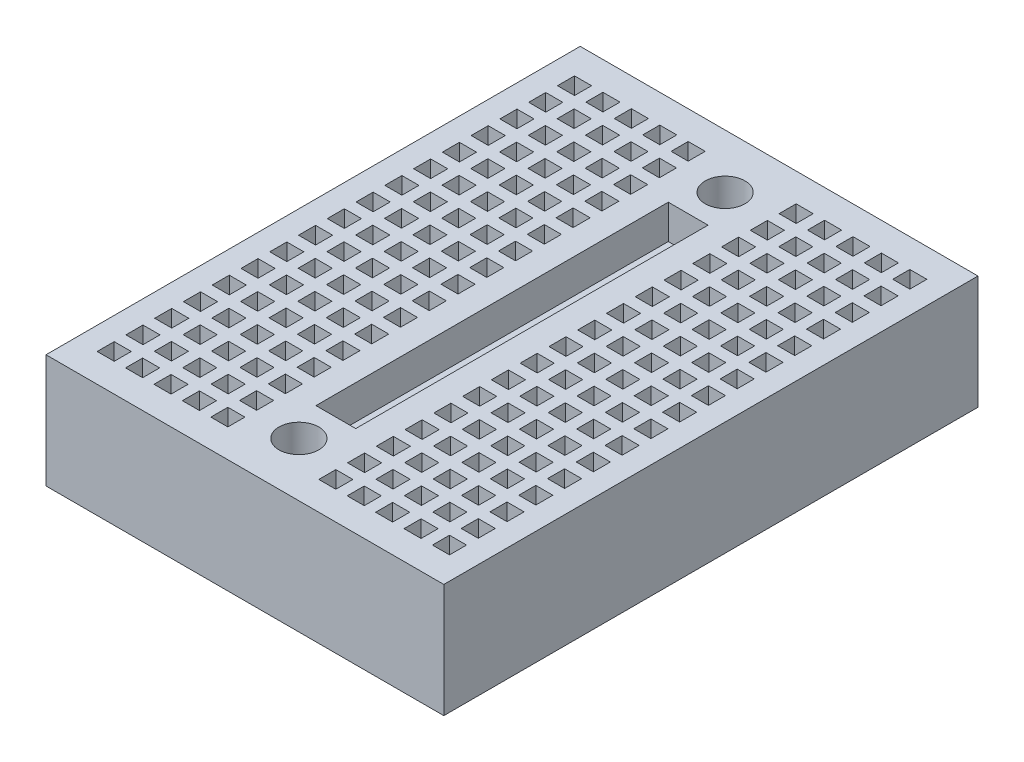
SolidWorks part; units mm, degrees
ref_plane "Front Plane" through (0, 0, 0) normal (0, 0, 1) x (1, 0, 0)
ref_plane "Top Plane" through (0, 0, 0) normal (0, 1, 0) x (1, 0, 0)
ref_plane "Right Plane" through (0, 0, 0) normal (1, 0, 0) x (0, 0, -1)
sketch "Sketch2" plane through (0, 0, 0) normal (0, 1, 0) x (1, 0, 0)
  line L1 (0, 23.5) -> (-17.5, 23.5)
  line L2 (0, 23.5) -> (0, -23.5)
  line L3 (0, -23.5) -> (-17.5, -23.5)
  line L4 (-17.5, 23.5) -> (-17.5, -23.5)
  line L5 (0, 23.5) -> (-17.5, -23.5) construction
  line L6 (0, -23.5) -> (-17.5, 23.5) construction
  point P0 (0, 0)
  point P6 (0, 0)
  point P7 (0, 0)
  dimension "D1" = 17.5
  dimension "D2" = 47
extrude "Boss-Extrude1" add sketch "Sketch2" along normal blind 7
sketch "Sketch3" plane through (0, 7, 0) normal (0, 1, 0) x (1, 0, 0)
  line L0 (0, -23.5) -> (0, 23.5) construction
  line L5 (1.75, -15.5) -> (-1.75, -15.5)
  line L6 (1.75, -15.5) -> (1.75, 15.5)
  line L7 (0, 23.5) -> (-17.5, 23.5) construction
  line L8 (-17.5, -23.5) -> (0, -23.5) construction
  line L9 (1.75, 15.5) -> (-1.75, 15.5)
  line L10 (-1.75, -15.5) -> (-1.75, 15.5)
  line L12 (-13, 21) -> (-13, 19.5)
  line L13 (-15.5, 21) -> (-14, 21)
  line L14 (-15.5, 21) -> (-15.5, 19.5)
  line L15 (-15.5, 19.5) -> (-14, 19.5)
  line L16 (-14, 21) -> (-14, 19.5)
  line L17 (-13, 21) -> (-11.5, 21)
  line L18 (-11.5, 21) -> (-11.5, 19.5)
  line L19 (-13, 19.5) -> (-11.5, 19.5)
  line L20 (-10.5, 21) -> (-10.5, 19.5)
  line L21 (-10.5, 21) -> (-9, 21)
  line L22 (-9, 21) -> (-9, 19.5)
  line L23 (-10.5, 19.5) -> (-9, 19.5)
  line L24 (-8, 21) -> (-8, 19.5)
  line L25 (-8, 21) -> (-6.5, 21)
  line L26 (-6.5, 21) -> (-6.5, 19.5)
  line L27 (-8, 19.5) -> (-6.5, 19.5)
  line L28 (-5.5, 21) -> (-5.5, 19.5)
  line L29 (-5.5, 21) -> (-4, 21)
  line L30 (-4, 21) -> (-4, 19.5)
  line L31 (-5.5, 19.5) -> (-4, 19.5)
  line L32 (-13, 18.4688) -> (-13, 16.9687)
  line L33 (-13, 18.4688) -> (-11.5, 18.4688)
  line L34 (-11.5, 18.4688) -> (-11.5, 16.9687)
  line L35 (-13, 16.9687) -> (-11.5, 16.9687)
  line L36 (-10.5, 18.4688) -> (-10.5, 16.9687)
  line L37 (-10.5, 18.4688) -> (-9, 18.4688)
  line L38 (-9, 18.4688) -> (-9, 16.9687)
  line L39 (-10.5, 16.9687) -> (-9, 16.9687)
  line L40 (-8, 18.4688) -> (-8, 16.9687)
  line L41 (-8, 18.4688) -> (-6.5, 18.4688)
  line L42 (-6.5, 18.4688) -> (-6.5, 16.9687)
  line L43 (-8, 16.9687) -> (-6.5, 16.9687)
  line L44 (-5.5, 18.4688) -> (-5.5, 16.9687)
  line L45 (-5.5, 18.4688) -> (-4, 18.4688)
  line L46 (-4, 18.4688) -> (-4, 16.9687)
  line L47 (-5.5, 16.9687) -> (-4, 16.9687)
  line L48 (-13, 15.9375) -> (-13, 14.4375)
  line L49 (-13, 15.9375) -> (-11.5, 15.9375)
  line L50 (-11.5, 15.9375) -> (-11.5, 14.4375)
  line L51 (-13, 14.4375) -> (-11.5, 14.4375)
  line L52 (-10.5, 15.9375) -> (-10.5, 14.4375)
  line L53 (-10.5, 15.9375) -> (-9, 15.9375)
  line L54 (-9, 15.9375) -> (-9, 14.4375)
  line L55 (-10.5, 14.4375) -> (-9, 14.4375)
  line L56 (-8, 15.9375) -> (-8, 14.4375)
  line L57 (-8, 15.9375) -> (-6.5, 15.9375)
  line L58 (-6.5, 15.9375) -> (-6.5, 14.4375)
  line L59 (-8, 14.4375) -> (-6.5, 14.4375)
  line L60 (-5.5, 15.9375) -> (-5.5, 14.4375)
  line L61 (-5.5, 15.9375) -> (-4, 15.9375)
  line L62 (-4, 15.9375) -> (-4, 14.4375)
  line L63 (-5.5, 14.4375) -> (-4, 14.4375)
  line L64 (-13, 13.4063) -> (-13, 11.9062)
  line L65 (-13, 13.4063) -> (-11.5, 13.4063)
  line L66 (-11.5, 13.4063) -> (-11.5, 11.9062)
  line L67 (-13, 11.9062) -> (-11.5, 11.9062)
  line L68 (-10.5, 13.4063) -> (-10.5, 11.9062)
  line L69 (-10.5, 13.4063) -> (-9, 13.4063)
  line L70 (-9, 13.4063) -> (-9, 11.9062)
  line L71 (-10.5, 11.9062) -> (-9, 11.9062)
  line L72 (-8, 13.4063) -> (-8, 11.9062)
  line L73 (-8, 13.4063) -> (-6.5, 13.4063)
  line L74 (-6.5, 13.4063) -> (-6.5, 11.9062)
  line L75 (-8, 11.9062) -> (-6.5, 11.9062)
  line L76 (-5.5, 13.4063) -> (-5.5, 11.9062)
  line L77 (-5.5, 13.4063) -> (-4, 13.4063)
  line L78 (-4, 13.4063) -> (-4, 11.9062)
  line L79 (-5.5, 11.9062) -> (-4, 11.9062)
  line L80 (-13, 10.875) -> (-13, 9.375)
  line L81 (-13, 10.875) -> (-11.5, 10.875)
  line L82 (-11.5, 10.875) -> (-11.5, 9.375)
  line L83 (-13, 9.375) -> (-11.5, 9.375)
  line L84 (-10.5, 10.875) -> (-10.5, 9.375)
  line L85 (-10.5, 10.875) -> (-9, 10.875)
  line L86 (-9, 10.875) -> (-9, 9.375)
  line L87 (-10.5, 9.375) -> (-9, 9.375)
  line L88 (-8, 10.875) -> (-8, 9.375)
  line L89 (-8, 10.875) -> (-6.5, 10.875)
  line L90 (-6.5, 10.875) -> (-6.5, 9.375)
  line L91 (-8, 9.375) -> (-6.5, 9.375)
  line L92 (-5.5, 10.875) -> (-5.5, 9.375)
  line L93 (-5.5, 10.875) -> (-4, 10.875)
  line L94 (-4, 10.875) -> (-4, 9.375)
  line L95 (-5.5, 9.375) -> (-4, 9.375)
  line L96 (-13, 8.3438) -> (-13, 6.8438)
  line L97 (-13, 8.3438) -> (-11.5, 8.3438)
  line L98 (-11.5, 8.3438) -> (-11.5, 6.8438)
  line L99 (-13, 6.8438) -> (-11.5, 6.8438)
  line L100 (-10.5, 8.3438) -> (-10.5, 6.8438)
  line L101 (-10.5, 8.3438) -> (-9, 8.3438)
  line L102 (-9, 8.3438) -> (-9, 6.8438)
  line L103 (-10.5, 6.8438) -> (-9, 6.8438)
  line L104 (-8, 8.3438) -> (-8, 6.8438)
  line L105 (-8, 8.3438) -> (-6.5, 8.3438)
  line L106 (-6.5, 8.3438) -> (-6.5, 6.8438)
  line L107 (-8, 6.8438) -> (-6.5, 6.8438)
  line L108 (-5.5, 8.3438) -> (-5.5, 6.8438)
  line L109 (-5.5, 8.3438) -> (-4, 8.3438)
  line L110 (-4, 8.3438) -> (-4, 6.8438)
  line L111 (-5.5, 6.8438) -> (-4, 6.8438)
  line L112 (-13, 5.8125) -> (-13, 4.3125)
  line L113 (-13, 5.8125) -> (-11.5, 5.8125)
  line L114 (-11.5, 5.8125) -> (-11.5, 4.3125)
  line L115 (-13, 4.3125) -> (-11.5, 4.3125)
  line L116 (-10.5, 5.8125) -> (-10.5, 4.3125)
  line L117 (-10.5, 5.8125) -> (-9, 5.8125)
  line L118 (-9, 5.8125) -> (-9, 4.3125)
  line L119 (-10.5, 4.3125) -> (-9, 4.3125)
  line L120 (-8, 5.8125) -> (-8, 4.3125)
  line L121 (-8, 5.8125) -> (-6.5, 5.8125)
  line L122 (-6.5, 5.8125) -> (-6.5, 4.3125)
  line L123 (-8, 4.3125) -> (-6.5, 4.3125)
  line L124 (-5.5, 5.8125) -> (-5.5, 4.3125)
  line L125 (-5.5, 5.8125) -> (-4, 5.8125)
  line L126 (-4, 5.8125) -> (-4, 4.3125)
  line L127 (-5.5, 4.3125) -> (-4, 4.3125)
  line L128 (-13, 3.2813) -> (-13, 1.7813)
  line L129 (-13, 3.2813) -> (-11.5, 3.2813)
  line L130 (-11.5, 3.2813) -> (-11.5, 1.7813)
  line L131 (-13, 1.7813) -> (-11.5, 1.7813)
  line L132 (-10.5, 3.2813) -> (-10.5, 1.7813)
  line L133 (-10.5, 3.2813) -> (-9, 3.2813)
  line L134 (-9, 3.2813) -> (-9, 1.7813)
  line L135 (-10.5, 1.7813) -> (-9, 1.7813)
  line L136 (-8, 3.2813) -> (-8, 1.7813)
  line L137 (-8, 3.2813) -> (-6.5, 3.2813)
  line L138 (-6.5, 3.2813) -> (-6.5, 1.7813)
  line L139 (-8, 1.7813) -> (-6.5, 1.7813)
  line L140 (-5.5, 3.2813) -> (-5.5, 1.7813)
  line L141 (-5.5, 3.2813) -> (-4, 3.2813)
  line L142 (-4, 3.2813) -> (-4, 1.7813)
  line L143 (-5.5, 1.7813) -> (-4, 1.7813)
  line L144 (-13, 0.75) -> (-13, -0.75)
  line L145 (-13, 0.75) -> (-11.5, 0.75)
  line L146 (-11.5, 0.75) -> (-11.5, -0.75)
  line L147 (-13, -0.75) -> (-11.5, -0.75)
  line L148 (-10.5, 0.75) -> (-10.5, -0.75)
  line L149 (-10.5, 0.75) -> (-9, 0.75)
  line L150 (-9, 0.75) -> (-9, -0.75)
  line L151 (-10.5, -0.75) -> (-9, -0.75)
  line L152 (-8, 0.75) -> (-8, -0.75)
  line L153 (-8, 0.75) -> (-6.5, 0.75)
  line L154 (-6.5, 0.75) -> (-6.5, -0.75)
  line L155 (-8, -0.75) -> (-6.5, -0.75)
  line L156 (-5.5, 0.75) -> (-5.5, -0.75)
  line L157 (-5.5, 0.75) -> (-4, 0.75)
  line L158 (-4, 0.75) -> (-4, -0.75)
  line L159 (-5.5, -0.75) -> (-4, -0.75)
  line L160 (-13, -1.7812) -> (-13, -3.2812)
  line L161 (-13, -1.7812) -> (-11.5, -1.7812)
  line L162 (-11.5, -1.7812) -> (-11.5, -3.2812)
  line L163 (-13, -3.2812) -> (-11.5, -3.2812)
  line L164 (-10.5, -1.7812) -> (-10.5, -3.2812)
  line L165 (-10.5, -1.7812) -> (-9, -1.7812)
  line L166 (-9, -1.7812) -> (-9, -3.2812)
  line L167 (-10.5, -3.2812) -> (-9, -3.2812)
  line L168 (-8, -1.7812) -> (-8, -3.2812)
  line L169 (-8, -1.7812) -> (-6.5, -1.7812)
  line L170 (-6.5, -1.7812) -> (-6.5, -3.2812)
  line L171 (-8, -3.2812) -> (-6.5, -3.2812)
  line L172 (-5.5, -1.7812) -> (-5.5, -3.2812)
  line L173 (-5.5, -1.7812) -> (-4, -1.7812)
  line L174 (-4, -1.7812) -> (-4, -3.2812)
  line L175 (-5.5, -3.2812) -> (-4, -3.2812)
  line L176 (-13, -4.3125) -> (-13, -5.8125)
  line L177 (-13, -4.3125) -> (-11.5, -4.3125)
  line L178 (-11.5, -4.3125) -> (-11.5, -5.8125)
  line L179 (-13, -5.8125) -> (-11.5, -5.8125)
  line L180 (-10.5, -4.3125) -> (-10.5, -5.8125)
  line L181 (-10.5, -4.3125) -> (-9, -4.3125)
  line L182 (-9, -4.3125) -> (-9, -5.8125)
  line L183 (-10.5, -5.8125) -> (-9, -5.8125)
  line L184 (-8, -4.3125) -> (-8, -5.8125)
  line L185 (-8, -4.3125) -> (-6.5, -4.3125)
  line L186 (-6.5, -4.3125) -> (-6.5, -5.8125)
  line L187 (-8, -5.8125) -> (-6.5, -5.8125)
  line L188 (-5.5, -4.3125) -> (-5.5, -5.8125)
  line L189 (-5.5, -4.3125) -> (-4, -4.3125)
  line L190 (-4, -4.3125) -> (-4, -5.8125)
  line L191 (-5.5, -5.8125) -> (-4, -5.8125)
  line L192 (-13, -6.8437) -> (-13, -8.3437)
  line L193 (-13, -6.8437) -> (-11.5, -6.8437)
  line L194 (-11.5, -6.8437) -> (-11.5, -8.3437)
  line L195 (-13, -8.3437) -> (-11.5, -8.3437)
  line L196 (-10.5, -6.8437) -> (-10.5, -8.3437)
  line L197 (-10.5, -6.8437) -> (-9, -6.8437)
  line L198 (-9, -6.8437) -> (-9, -8.3437)
  line L199 (-10.5, -8.3437) -> (-9, -8.3437)
  line L200 (-8, -6.8437) -> (-8, -8.3437)
  line L201 (-8, -6.8437) -> (-6.5, -6.8437)
  line L202 (-6.5, -6.8437) -> (-6.5, -8.3437)
  line L203 (-8, -8.3437) -> (-6.5, -8.3437)
  line L204 (-5.5, -6.8437) -> (-5.5, -8.3437)
  line L205 (-5.5, -6.8437) -> (-4, -6.8437)
  line L206 (-4, -6.8437) -> (-4, -8.3437)
  line L207 (-5.5, -8.3437) -> (-4, -8.3437)
  line L208 (-13, -9.375) -> (-13, -10.875)
  line L209 (-13, -9.375) -> (-11.5, -9.375)
  line L210 (-11.5, -9.375) -> (-11.5, -10.875)
  line L211 (-13, -10.875) -> (-11.5, -10.875)
  line L212 (-10.5, -9.375) -> (-10.5, -10.875)
  line L213 (-10.5, -9.375) -> (-9, -9.375)
  line L214 (-9, -9.375) -> (-9, -10.875)
  line L215 (-10.5, -10.875) -> (-9, -10.875)
  line L216 (-8, -9.375) -> (-8, -10.875)
  line L217 (-8, -9.375) -> (-6.5, -9.375)
  line L218 (-6.5, -9.375) -> (-6.5, -10.875)
  line L219 (-8, -10.875) -> (-6.5, -10.875)
  line L220 (-5.5, -9.375) -> (-5.5, -10.875)
  line L221 (-5.5, -9.375) -> (-4, -9.375)
  line L222 (-4, -9.375) -> (-4, -10.875)
  line L223 (-5.5, -10.875) -> (-4, -10.875)
  line L224 (-13, -11.9062) -> (-13, -13.4062)
  line L225 (-13, -11.9062) -> (-11.5, -11.9062)
  line L226 (-11.5, -11.9062) -> (-11.5, -13.4062)
  line L227 (-13, -13.4062) -> (-11.5, -13.4062)
  line L228 (-10.5, -11.9062) -> (-10.5, -13.4062)
  line L229 (-10.5, -11.9062) -> (-9, -11.9062)
  line L230 (-9, -11.9062) -> (-9, -13.4062)
  line L231 (-10.5, -13.4062) -> (-9, -13.4062)
  line L232 (-8, -11.9062) -> (-8, -13.4062)
  line L233 (-8, -11.9062) -> (-6.5, -11.9062)
  line L234 (-6.5, -11.9062) -> (-6.5, -13.4062)
  line L235 (-8, -13.4062) -> (-6.5, -13.4062)
  line L236 (-5.5, -11.9062) -> (-5.5, -13.4062)
  line L237 (-5.5, -11.9062) -> (-4, -11.9062)
  line L238 (-4, -11.9062) -> (-4, -13.4062)
  line L239 (-5.5, -13.4062) -> (-4, -13.4062)
  line L240 (-13, -14.4375) -> (-13, -15.9375)
  line L241 (-13, -14.4375) -> (-11.5, -14.4375)
  line L242 (-11.5, -14.4375) -> (-11.5, -15.9375)
  line L243 (-13, -15.9375) -> (-11.5, -15.9375)
  line L244 (-10.5, -14.4375) -> (-10.5, -15.9375)
  line L245 (-10.5, -14.4375) -> (-9, -14.4375)
  line L246 (-9, -14.4375) -> (-9, -15.9375)
  line L247 (-10.5, -15.9375) -> (-9, -15.9375)
  line L248 (-8, -14.4375) -> (-8, -15.9375)
  line L249 (-8, -14.4375) -> (-6.5, -14.4375)
  line L250 (-6.5, -14.4375) -> (-6.5, -15.9375)
  line L251 (-8, -15.9375) -> (-6.5, -15.9375)
  line L252 (-5.5, -14.4375) -> (-5.5, -15.9375)
  line L253 (-5.5, -14.4375) -> (-4, -14.4375)
  line L254 (-4, -14.4375) -> (-4, -15.9375)
  line L255 (-5.5, -15.9375) -> (-4, -15.9375)
  line L256 (-13, -16.9687) -> (-13, -18.4687)
  line L257 (-13, -16.9687) -> (-11.5, -16.9687)
  line L258 (-11.5, -16.9687) -> (-11.5, -18.4687)
  line L259 (-13, -18.4687) -> (-11.5, -18.4687)
  line L260 (-10.5, -16.9687) -> (-10.5, -18.4687)
  line L261 (-10.5, -16.9687) -> (-9, -16.9687)
  line L262 (-9, -16.9687) -> (-9, -18.4687)
  line L263 (-10.5, -18.4687) -> (-9, -18.4687)
  line L264 (-8, -16.9687) -> (-8, -18.4687)
  line L265 (-8, -16.9687) -> (-6.5, -16.9687)
  line L266 (-6.5, -16.9687) -> (-6.5, -18.4687)
  line L267 (-8, -18.4687) -> (-6.5, -18.4687)
  line L268 (-5.5, -16.9687) -> (-5.5, -18.4687)
  line L269 (-5.5, -16.9687) -> (-4, -16.9687)
  line L270 (-4, -16.9687) -> (-4, -18.4687)
  line L271 (-5.5, -18.4687) -> (-4, -18.4687)
  line L272 (-13, -19.5) -> (-13, -21)
  line L273 (-13, -19.5) -> (-11.5, -19.5)
  line L274 (-11.5, -19.5) -> (-11.5, -21)
  line L275 (-13, -21) -> (-11.5, -21)
  line L276 (-10.5, -19.5) -> (-10.5, -21)
  line L277 (-10.5, -19.5) -> (-9, -19.5)
  line L278 (-9, -19.5) -> (-9, -21)
  line L279 (-10.5, -21) -> (-9, -21)
  line L280 (-8, -19.5) -> (-8, -21)
  line L281 (-8, -19.5) -> (-6.5, -19.5)
  line L282 (-6.5, -19.5) -> (-6.5, -21)
  line L283 (-8, -21) -> (-6.5, -21)
  line L284 (-5.5, -19.5) -> (-5.5, -21)
  line L285 (-5.5, -19.5) -> (-4, -19.5)
  line L286 (-4, -19.5) -> (-4, -21)
  line L287 (-5.5, -21) -> (-4, -21)
  line L288 (-15.5, 18.4688) -> (-15.5, 16.9687)
  line L289 (-15.5, 18.4688) -> (-14, 18.4688)
  line L290 (-14, 18.4688) -> (-14, 16.9687)
  line L291 (-15.5, 16.9687) -> (-14, 16.9687)
  line L292 (-15.5, 15.9375) -> (-15.5, 14.4375)
  line L293 (-15.5, 15.9375) -> (-14, 15.9375)
  line L294 (-14, 15.9375) -> (-14, 14.4375)
  line L295 (-15.5, 14.4375) -> (-14, 14.4375)
  line L296 (-15.5, 13.4063) -> (-15.5, 11.9062)
  line L297 (-15.5, 13.4063) -> (-14, 13.4063)
  line L298 (-14, 13.4063) -> (-14, 11.9062)
  line L299 (-15.5, 11.9062) -> (-14, 11.9062)
  line L300 (-15.5, 10.875) -> (-15.5, 9.375)
  line L301 (-15.5, 10.875) -> (-14, 10.875)
  line L302 (-14, 10.875) -> (-14, 9.375)
  line L303 (-15.5, 9.375) -> (-14, 9.375)
  line L304 (-15.5, 8.3438) -> (-15.5, 6.8438)
  line L305 (-15.5, 8.3438) -> (-14, 8.3438)
  line L306 (-14, 8.3438) -> (-14, 6.8438)
  line L307 (-15.5, 6.8438) -> (-14, 6.8438)
  line L308 (-15.5, 5.8125) -> (-15.5, 4.3125)
  line L309 (-15.5, 5.8125) -> (-14, 5.8125)
  line L310 (-14, 5.8125) -> (-14, 4.3125)
  line L311 (-15.5, 4.3125) -> (-14, 4.3125)
  line L312 (-15.5, 3.2813) -> (-15.5, 1.7813)
  line L313 (-15.5, 3.2813) -> (-14, 3.2813)
  line L314 (-14, 3.2813) -> (-14, 1.7813)
  line L315 (-15.5, 1.7813) -> (-14, 1.7813)
  line L316 (-15.5, 0.75) -> (-15.5, -0.75)
  line L317 (-15.5, 0.75) -> (-14, 0.75)
  line L318 (-14, 0.75) -> (-14, -0.75)
  line L319 (-15.5, -0.75) -> (-14, -0.75)
  line L320 (-15.5, -1.7812) -> (-15.5, -3.2812)
  line L321 (-15.5, -1.7812) -> (-14, -1.7812)
  line L322 (-14, -1.7812) -> (-14, -3.2812)
  line L323 (-15.5, -3.2812) -> (-14, -3.2812)
  line L324 (-15.5, -4.3125) -> (-15.5, -5.8125)
  line L325 (-15.5, -4.3125) -> (-14, -4.3125)
  line L326 (-14, -4.3125) -> (-14, -5.8125)
  line L327 (-15.5, -5.8125) -> (-14, -5.8125)
  line L328 (-15.5, -6.8437) -> (-15.5, -8.3437)
  line L329 (-15.5, -6.8437) -> (-14, -6.8437)
  line L330 (-14, -6.8437) -> (-14, -8.3437)
  line L331 (-15.5, -8.3437) -> (-14, -8.3437)
  line L332 (-15.5, -9.375) -> (-15.5, -10.875)
  line L333 (-15.5, -9.375) -> (-14, -9.375)
  line L334 (-14, -9.375) -> (-14, -10.875)
  line L335 (-15.5, -10.875) -> (-14, -10.875)
  line L336 (-15.5, -11.9062) -> (-15.5, -13.4062)
  line L337 (-15.5, -11.9062) -> (-14, -11.9062)
  line L338 (-14, -11.9062) -> (-14, -13.4062)
  line L339 (-15.5, -13.4062) -> (-14, -13.4062)
  line L340 (-15.5, -14.4375) -> (-15.5, -15.9375)
  line L341 (-15.5, -14.4375) -> (-14, -14.4375)
  line L342 (-14, -14.4375) -> (-14, -15.9375)
  line L343 (-15.5, -15.9375) -> (-14, -15.9375)
  line L344 (-15.5, -16.9687) -> (-15.5, -18.4687)
  line L345 (-15.5, -16.9687) -> (-14, -16.9687)
  line L346 (-14, -16.9687) -> (-14, -18.4687)
  line L347 (-15.5, -18.4687) -> (-14, -18.4687)
  line L348 (-15.5, -19.5) -> (-15.5, -21)
  line L349 (-15.5, -19.5) -> (-14, -19.5)
  line L350 (-14, -19.5) -> (-14, -21)
  line L351 (-15.5, -21) -> (-14, -21)
  line L352 (-17.5, 23.5) -> (-17.5, -23.5) construction
  line L353 (-9.75, 21) -> (-9.75, 23.5) construction
  line L354 (-9.75, -21) -> (-9.75, -23.5) construction
  line L355 (1.75, -15.5) -> (-1.75, 15.5) construction
  line L356 (1.75, 15.5) -> (-1.75, -15.5) construction
  line L357 (0, 20.5) -> (0, 23.5) construction
  line L358 (0, 0) -> (-17.5, 0) construction
  circle A4 centre (0, 18.75) radius 1.75
  circle A5 centre (0, -18.75) radius 1.75
  point P0 (0, 0)
  point P1 (0, 0)
  point P36 (-4, 0)
  line M352 (-17.5, 23.5) -> (-17.5, -23.5)
  line M353 (-17.5, -23.5) -> (0, -23.5)
  line M354 (0, -23.5) -> (0, 23.5)
  line M355 (0, 23.5) -> (-17.5, 23.5)
  dimension "D3" = 3
  dimension "D4" = 31
  dimension "D2" = 3.5
  dimension "D5" = 3.5
  dimension "D6" = 1.5
  dimension "D9" = 11.5
  dimension "D10" = 42
  dimension "D11" = 2
  dimension "D7" = 5
  dimension "D8" = 17
extrude "Boss-Extrude2" add sketch "Sketch3" along normal blind 3 contours A4 L5 L10 L9 L351 L348 L349 L350 L347 L344 L345 L346 L343 L340 L341 L342 L339 L336 L337 L338 L335 L332 L333 L334 L331 L328 L329 L330 L327 L324 L325 L326 L323 L320 L321 L322 M354 M355 M352 M353 region at (-0.5015, 7, 16.25)
mirror "Mirror1" about plane through (0, 7, -23.5) normal (-1, 0, 0) of "Boss-Extrude2", "Boss-Extrude1"
